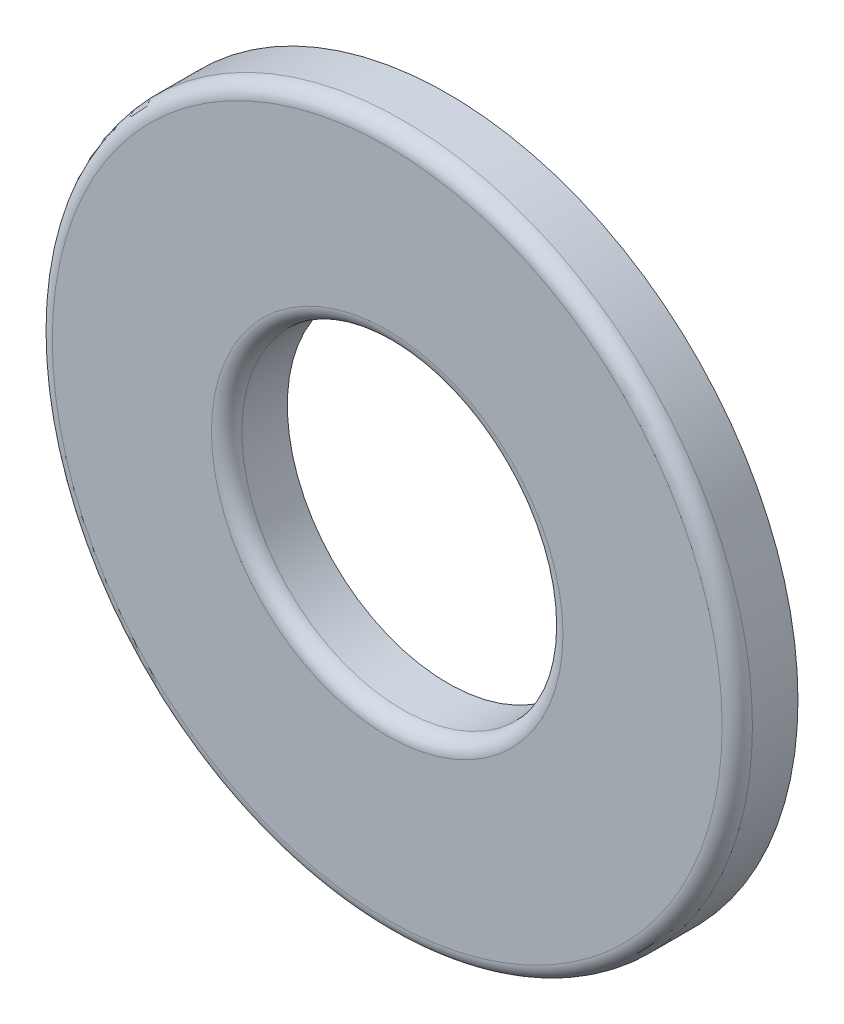
SolidWorks part; units mm, degrees
note: '?' marks a value the reader was unsure of.
other "Imported1" parameters "D1"=0.2064, "TH"=1.0287, "Thickness"=0.8255
ref_plane "Front Plane" through (0, 0, 0) normal (0, 0, 1) x (1, 0, 0)
ref_plane "Top Plane" through (0, 0, 0) normal (0, 1, 0) x (1, 0, 0)
ref_plane "Right Plane" through (0, 0, 0) normal (1, 0, 0) x (0, 0, -1)
sketch "Sketch1" plane through (0, 0, 0) normal (0, 0, 1) x (1, 0, 0)
  line L0 (-4.7625, 0) -> (4.7625, 0) construction
  line L1 (-2.1844, 0) -> (2.1844, 0) construction
  circle A0 centre (0, 0) radius 2.1844 construction
  circle A1 centre (0, 0) radius 4.7625 construction
  point P8 (0, 0)
  point P9 (0, 4.7625)
  point P11 (2.1844, 0)
  dimension "ID" = 4.3688
  dimension "OD" = 9.525
sketch "Sketch2" plane through (0, 0, 0) normal (1, 0, 0) x (0, 0, -1)
  line L0 (-0.4127, 4.7625) -> (0.4128, 4.7625) construction
  point P2 (0, 4.7625)
sketch "Sketch3" plane through (0, 0, 0) normal (0, 0, 1) x (1, 0, 0)
  circle A0 centre (0, 0) radius 2.1844
  circle A1 centre (0, 0) radius 4.7625
extrude "Boss-Extrude1" add sketch "Sketch3" along normal up to vertex (0.4128 mm away) and the other way up to vertex (0.4128 mm away) up to point (0, 4.7625, 0.4127) other way up to point (0, 4.7625, -0.4128)
fillet "Fillet1" radius 0.2064 2 edges at (4.7625, 0, 0.4127) (2.1844, 0, 0.4127)
ref_axis "Center Axis 1" through (0, 0, 0.2064) along (0, 0, -1)?
equation "\"D1@Fillet1\"=\"Thickness@Sketch2\"/4"
